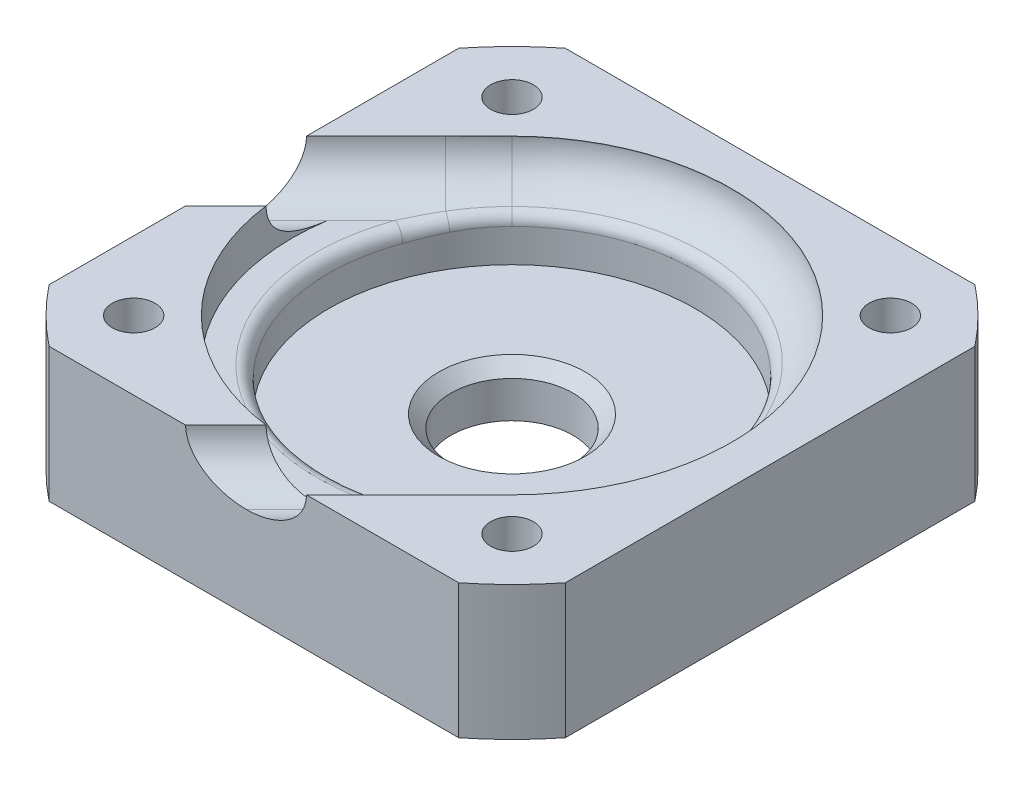
SolidWorks part; units mm, degrees
ref_plane "Front Plane" through (0, 0, 0) normal (0, 0, 1) x (1, 0, 0)
ref_plane "Top Plane" through (0, 0, 0) normal (0, 1, 0) x (1, 0, 0)
ref_plane "Right Plane" through (0, 0, 0) normal (1, 0, 0) x (0, 0, -1)
sketch "Sketch2" plane through (0, 0, 0) normal (0, 1, 0) x (1, 0, 0)
  line L1 (-21.15, 21.15) -> (21.15, 21.15)
  line L2 (-21.15, 21.15) -> (-21.15, -21.15)
  line L3 (-21.15, -21.15) -> (21.15, -21.15)
  line L4 (21.15, 21.15) -> (21.15, -21.15)
  line L5 (-21.15, 21.15) -> (21.15, -21.15) construction
  line L6 (-21.15, -21.15) -> (21.15, 21.15) construction
  point P0 (0, 0)
  dimension "D1" = 42.3
extrude "Boss-Extrude1" add sketch "Sketch2" along normal blind 11
sketch "Sketch3" plane through (0, 11, 0) normal (0, 1, 0) x (1, 0, 0)
  circle A0 centre (0, 0) radius 3
  dimension "D1" = 6
extrude "Cut-Extrude1" cut sketch "Sketch3" against normal through all
sketch "Sketch4" plane through (0, 11, 0) normal (0, 1, 0) x (1, 0, 0)
  line L1 (-15.5, 15.5) -> (15.5, 15.5) construction
  line L2 (-15.5, 15.5) -> (-15.5, -15.5) construction
  line L3 (-15.5, -15.5) -> (15.5, -15.5) construction
  line L4 (15.5, 15.5) -> (15.5, -15.5) construction
  line L5 (-15.5, 15.5) -> (15.5, -15.5) construction
  line L6 (-15.5, -15.5) -> (15.5, 15.5) construction
  circle A0 centre (-15.5, 15.5) radius 1.75
  circle A1 centre (15.5, 15.5) radius 1.75
  circle A2 centre (15.5, -15.5) radius 1.75
  circle A3 centre (-15.5, -15.5) radius 1.75
  point P0 (0, 0)
  point P16 (0, 0)
  dimension "D3" = 3.5
  dimension "D1" = 31
  dimension "D2" = 31
  dimension "D4" = 4
extrude "Cut-Extrude2" cut sketch "Sketch4" against normal through all
sketch "Sketch5" plane through (0, 11, 0) normal (0, 1, 0) x (1, 0, 0)
  circle A0 centre (0, 0) radius 27
  circle A1 centre (0, 0) radius 29.9106
  dimension "D1" = 54
extrude "Cut-Extrude4" cut sketch "Sketch5" against normal through all
sketch "Sketch6" plane through (0, 11, 0) normal (0, 1, 0) x (1, 0, 0)
  line L0 (-21.15, 4.3058) -> (-12.7279, 12.7279)
  line L1 (12.7279, -12.7279) -> (4.3058, -21.15)
  line L9 (-21.15, 16.7833) -> (-21.15, -16.7833) construction
  line L10 (-16.7833, -21.15) -> (16.7833, -21.15) construction
  line L11 (-7.7782, 7.7782) -> (-21.15, -5.5937) construction
  line L12 (4.3058, 21.15) -> (21.15, 4.3058) construction
  line L13 (7.3751, 21.15) -> (21.15, 7.3751) construction
  line L14 (16.7833, 21.15) -> (-16.7833, 21.15) construction
  line L15 (21.15, -16.7833) -> (21.15, 16.7833) construction
  line L18 (7.7782, -7.7782) -> (-5.5937, -21.15) construction
  line L19 (-21.15, 4.3058) -> (-21.15, -5.5937)
  line L21 (-2.2965, -17.8529) -> (-5.5937, -21.15)
  line L22 (-5.5937, -21.15) -> (4.3058, -21.15)
  line L23 (-17.8529, -2.2965) -> (-21.15, -5.5937)
  arc A0 (-12.7279, 12.7279) -> (12.7279, -12.7279) centre (0, 0) cw
  arc A2 (-17.8529, -2.2965) -> (-2.2965, -17.8529) centre (0, 0) ccw
  circle A3 centre (0, 0) radius 11 construction
  circle A5 centre (15.5, 15.5) radius 1.75 construction
  arc A6 (12.7279, -12.7279) -> (-12.7279, 12.7279) centre (0, 0) ccw
  circle M13 centre (0, 0) radius 3
  line M14 (-16.7833, -21.15) -> (16.7833, -21.15)
  line M20 (-21.15, 16.7833) -> (-21.15, -16.7833)
  dimension "D1" = 45
  dimension "D3" = 18
  dimension "D5" = 22
  dimension "D2" = 45
  dimension "D4" = 45
extrude "Cut-Extrude5" cut sketch "Sketch6" against normal offset from surface (7 mm away) 4 contours L23 A2 L21 L1 A0 L0 M14 M20 M13 region at (-16.5475, 11, -8.1254) up to face at (-15.5, 0, 17.25)
chamfer "Chamfer1" distance 1.8 angle 45 4 edges at (15.5, 0, -13.75) (-15.5, 0, -13.75) (-15.5, 0, 17.25) (15.5, 0, 17.25)
sketch "Sketch7" plane through (0, 4, 0) normal (0, 1, 0) x (1, 0, 0)
  circle A0 centre (0, 0) radius 5
  dimension "D1" = 10
extrude "Cut-Extrude6" cut sketch "Sketch7" against normal through all
sketch "Sketch8" plane through (0, 4, 0) normal (0, 1, 0) x (1, 0, 0)
  line L6 (-21.15, 4.3058) -> (-21.15, -5.5937)
  line L7 (-21.15, -5.5937) -> (-17.8529, -2.2965)
  line L8 (-2.2965, -17.8529) -> (-5.5937, -21.15)
  line L9 (-5.5937, -21.15) -> (4.3058, -21.15)
  line L10 (4.3058, -21.15) -> (12.7279, -12.7279)
  line L11 (-12.7279, 12.7279) -> (-21.15, 4.3058)
  line L12 (-21.15, 4.3058) -> (-21.15, -5.5937)
  line L13 (-21.15, -5.5937) -> (-17.8529, -2.2965)
  line L14 (-2.2965, -17.8529) -> (-5.5937, -21.15)
  line L15 (-5.5937, -21.15) -> (4.3058, -21.15)
  line L16 (4.3058, -21.15) -> (12.7279, -12.7279)
  line L17 (-12.7279, 12.7279) -> (-21.15, 4.3058)
  circle A0 centre (0, 0) radius 15
  arc A3 (-17.8529, -2.2965) -> (-2.2965, -17.8529) centre (0, 0) ccw
  arc A4 (12.7279, -12.7279) -> (-12.7279, 12.7279) centre (0, 0) ccw
  arc A5 (-17.8529, -2.2965) -> (-2.2965, -17.8529) centre (0, 0) ccw
  arc A6 (12.7279, -12.7279) -> (-12.7279, 12.7279) centre (0, 0) ccw
  dimension "D1" = 30
  dimension "D2" = 0
extrude "Boss-Extrude2" add sketch "Sketch8" along normal offset from surface (3.5 mm away) 3.5 up to face at (-15.5, 11, -13.75)
fillet "Fillet1" radius 3.5 4 edges at (8.5169, 7.5, 16.939) (-16.939, 7.5, -8.5169) (-19.5014, 7.5, 3.9451) (-3.9451, 7.5, 19.5014)
chamfer "Chamfer2" distance 1 angle 45 1 edges at (0, 4, 5)
fillet "Fillet2" radius 1 4 edges at (9.1485, 7.5, 11.8871) (-10.6066, 7.5, 10.6066) (-11.8871, 7.5, -9.1485) (10.6066, 7.5, -10.6066)
